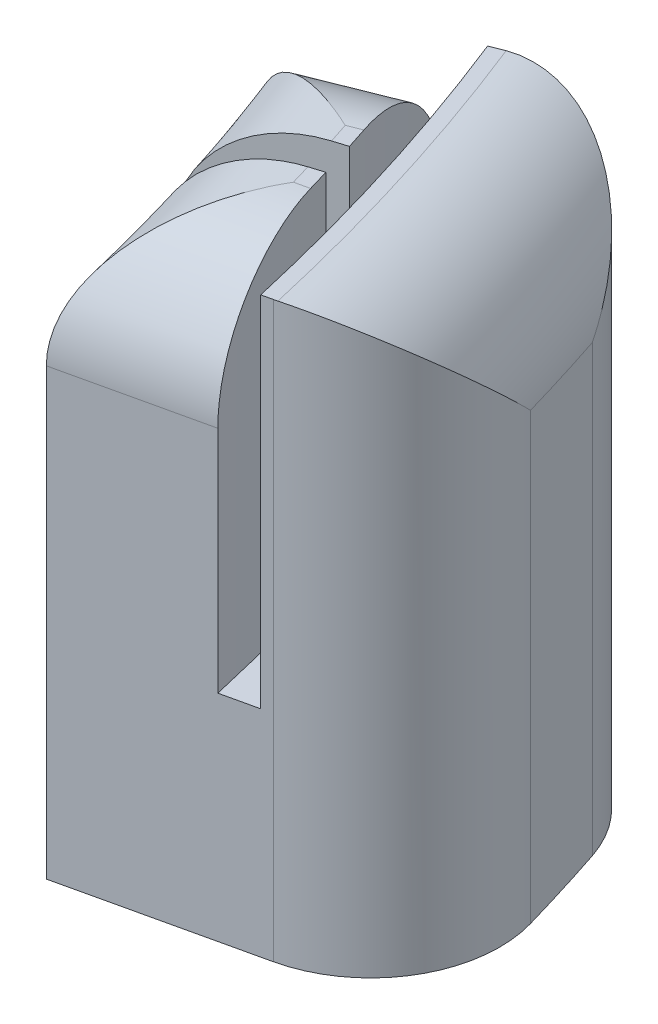
SolidWorks part; units mm, degrees
ref_plane "前视基准面" through (0, 0, 0) normal (0, 0, 1) x (1, 0, 0)
ref_plane "上视基准面" through (0, 0, 0) normal (0, 1, 0) x (1, 0, 0)
ref_plane "右视基准面" through (0, 0, 0) normal (1, 0, 0) x (0, 0, -1)
sketch "草图1" plane through (0, 0, 0) normal (0, 1, 0) x (1, 0, 0)
  line L0 (0, 0) -> (1446.9337, 449.0077) construction
  line L1 (10.5951, 16.3759) -> (1443.1798, 460.9308) construction
  line L2 (10.4346, -9.85) -> (1450.5891, 437.054) construction
  line L6 (1477.5429, 334.8014) -> (1380.0153, 312.7023)
  line L7 (0, 0) -> (1477.5429, 334.8014) construction
  line L10 (1407.5113, 560.4791) -> (1314.6063, 523.4838)
  line L11 (1407.5113, 560.4791) -> (1314.6063, 523.4838)
  line L12 (1430.7376, 569.7279) -> (1523.6426, 606.7232)
  line L13 (1501.9248, 340.3261) -> (1599.4524, 362.4252)
  line L14 (1477.5429, 334.8014) -> (1501.9248, 340.3261)
  line L15 (1430.7376, 569.7279) -> (1407.5113, 560.4791)
  circle A1 centre (0, 0) radius 1540 construction
  arc A2 (1443.1798, 460.9308) -> (1407.5113, 560.4791) centre (0, 0) ccw construction
  arc A3 (1450.5891, 437.054) -> (1477.5429, 334.8014) centre (0, 0) cw construction
  arc A7 (1314.6063, 523.4838) -> (1347.6691, 431.2922) centre (0, 0) cw
  arc A8 (1380.0153, 312.7023) -> (1355.0785, 407.4154) centre (0, 0) ccw
  arc A9 (1523.6426, 606.7232) -> (1599.4524, 362.4252) centre (0, 0) cw
  arc A10 (1355.0785, 407.4154) -> (1347.6691, 431.2922) centre (0, 0) ccw
  dimension "D1" = 4.473
  dimension "D2" = 3080
  dimension "D3" = 12.5
  dimension "D6" = 100
  dimension "D4" = 12.5
  dimension "D7" = 100
  dimension "D8" = 100
  dimension "D9" = 4.473
extrude "凸台-拉伸1" add sketch "草图1" along normal blind 400 contours A10 A8 L6 L14 L13 A9 L12 L15 L10 A7 region at (1460.0259, 0, -453.0704)
sketch "草图2" plane through (0, 400, 0) normal (0, 1, 0) x (1, 0, 0)
  line L0 (0, 0) -> (1566.3177, 486.0545) construction
  line L1 (1297.7127, 415.7899) -> (1443.1798, 460.9308) construction
  line L2 (1380.0153, 312.7023) -> (1599.4524, 362.4252)
  line L3 (1523.6426, 606.7232) -> (1314.6063, 523.4838)
  line L4 (1380.0153, 312.7023) -> (1599.4524, 362.4252) construction
  line L5 (1523.6426, 606.7232) -> (1314.6063, 523.4838) construction
  line L6 (1308.5842, 392.9875) -> (1450.5891, 437.054) construction
  line L7 (1347.6691, 431.2922) -> (1443.1798, 460.9308)
  line L8 (1450.5891, 437.054) -> (1355.0785, 407.4154)
  line L9 (1407.5113, 560.4791) -> (1430.7376, 569.7279)
  line L10 (1477.5429, 334.8014) -> (1501.9248, 340.3261)
  circle A0 centre (0, 0) radius 1515 construction
  circle A1 centre (0, 0) radius 1540 construction
  arc A2 (1380.0153, 312.7023) -> (1314.6063, 523.4838) centre (0, 0) ccw
  arc A3 (1599.4524, 362.4252) -> (1523.6426, 606.7232) centre (0, 0) ccw
  arc A4 (1380.0153, 312.7023) -> (1314.6063, 523.4838) centre (0, 0) ccw construction
  arc A5 (1599.4524, 362.4252) -> (1523.6426, 606.7232) centre (0, 0) ccw construction
  arc A6 (1347.6691, 431.2922) -> (1355.0785, 407.4154) centre (0, 0) cw
  arc A7 (1443.1798, 460.9308) -> (1407.5113, 560.4791) centre (0, 0) ccw
  arc A8 (1450.5891, 437.054) -> (1477.5429, 334.8014) centre (0, 0) cw
  arc A9 (1430.7376, 569.7279) -> (1501.9248, 340.3261) centre (0, 0) cw
  dimension "D2" = 3030
  dimension "D3" = 3080
  dimension "D4" = 12.5
  dimension "D5" = 12.5
  dimension "D1" = 0
extrude "切除-拉伸1" cut sketch "草图2" against normal blind 250
sketch "草图3" plane through (0, 0, 0) normal (0, -1, 0) x (1, 0, 0)
  line L0 (0, 0) -> (1566.3177, -486.0545) construction
  line L1 (1599.4524, -362.4252) -> (1380.0153, -312.7023) construction
  line L2 (1314.6063, -523.4838) -> (1523.6426, -606.7232) construction
  line L3 (0, 0) -> (1496.5637, -537.0261) construction
  line L4 (0, 0) -> (1537.6738, -404.5484) construction
  arc A0 (1523.6426, -606.7232) -> (1599.4524, -362.4252) centre (0, 0) ccw construction
  arc A2 (1477.1901, -588.2256) -> (1550.6886, -351.3757) centre (0, 0) ccw construction
  circle A3 centre (1537.6738, -404.5484) radius 15.6654
  circle A4 centre (1496.5637, -537.0261) radius 18.5105
  dimension "D2" = 2.5
  dimension "D1" = 1590
  dimension "D3" = 2.5
extrude "切除-拉伸2" cut sketch "草图3" against normal blind 50
fillet "圆角2" radius 90 3 edges at (1566.3177, 400, -486.0545) (1599.4524, 200, -362.4252) (1523.6426, 200, -606.7232)
fillet "圆角3" radius 90 4 edges at (1428.7791, 400, -323.7518) (1368.3666, 400, -360.2747) (1361.0588, 400, -541.9814) (1331.9356, 400, -477.6741)
sketch "草图4" plane through (0, 50, 0) normal (0, -1, 0) x (1, 0, 0)
  circle A1 centre (1496.5637, -537.0261) radius 18.5105
  circle A2 centre (1496.5637, -537.0261) radius 18.5105
  circle A3 centre (1537.6738, -404.5484) radius 15.6654
  circle A4 centre (1537.6738, -404.5484) radius 15.6654
  dimension "D1" = 0
  dimension "D2" = 0
extrude "凸台-拉伸2" add sketch "草图4" along normal up to surface (50 mm away) up to face at (1496.5637, 0, -555.5366)
sketch "草图6" plane through (0, 0, 0) normal (0, -1, 0) x (1, 0, 0)
  line L0 (1351.4265, -419.3702) -> (1566.3177, -486.0545)
  arc A0 (1314.6063, -523.4838) -> (1380.0153, -312.7023) centre (0, 0) ccw construction
  arc A1 (1556.3011, -517.23) -> (1575.7098, -454.6852) centre (0, 0) ccw construction
sketch "草图8" plane through (0, 0, 0) normal (0, -1, 0) x (1, 0, 0)
  line L1 (1509.1271, -341.9581) -> (1380.0153, -312.7023) construction
  line L2 (1314.6063, -523.4838) -> (1437.5985, -572.46) construction
  circle A0 centre (1431.5348, -375.6438) radius 25
  arc A2 (1314.6063, -523.4838) -> (1380.0153, -312.7023) centre (0, 0) ccw construction
  circle A4 centre (1392.7073, -500.7657) radius 25
  dimension "D1" = 50
  dimension "D4" = 50
  dimension "D2" = 1480
  dimension "D3" = 50
  dimension "D5" = 1480
  dimension "D6" = 50
extrude "切除-拉伸3" cut sketch "草图8" against normal blind 100
